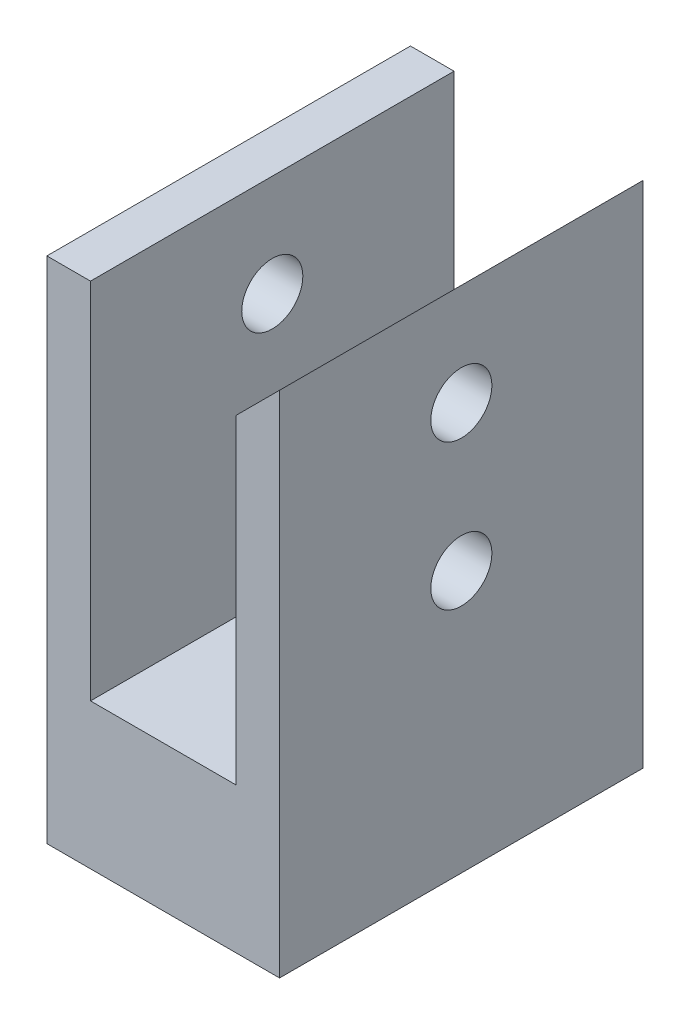
SolidWorks part; units mm, degrees
ref_plane "前视基准面" through (0, 0, 0) normal (0, 0, 1) x (1, 0, 0)
ref_plane "上视基准面" through (0, 0, 0) normal (0, 1, 0) x (1, 0, 0)
ref_plane "右视基准面" through (0, 0, 0) normal (1, 0, 0) x (0, 0, -1)
sketch "草图1" plane through (0, 0, 0) normal (0, 0, 1) x (1, 0, 0)
  line L0 (0, -55) -> (0, 55) construction
  line L1 (-8, -10) -> (8, -10)
  line L2 (-8, -10) -> (-8, 0)
  line L3 (-8, 0) -> (8, 0)
  line L4 (8, -10) -> (8, 0)
  line L5 (-8, -10) -> (8, 0) construction
  line L6 (-8, 0) -> (8, -10) construction
  line L7 (8, 0) -> (5, 0)
  line L8 (8, 0) -> (8, 25)
  line L9 (8, 25) -> (5, 25)
  line L10 (5, 0) -> (5, 25)
  line L11 (-8, 25) -> (-5, 25)
  line L12 (-5, 0) -> (-5, 25)
  line L13 (-8, 0) -> (-5, 0)
  line L14 (-8, 0) -> (-8, 25)
  line L15 (8, 25) -> (5, 22)
  point P0 (0, -5)
  point P14 (5, 22)
  dimension "D1" = 5
  dimension "D2" = 16
  dimension "D3" = 10
  dimension "D4" = 25
  dimension "D5" = 3
  dimension "D6" = 3
extrude "凸台-拉伸1" add sketch "草图1" along normal blind 25 contours L14 L3 L12 L11 | L10 L3 L8 L9 | L1 L4 L3 L2 region at (0, -5, 0) region at (-6.5, 12.5, 0) region at (6.5319, 11.766, 0)
sketch "草图2" plane through (0, 0, 0) normal (1, 0, 0) x (0, 0, -1)
  line L0 (0, -10) -> (0, 25) construction
  circle A0 centre (-12.5, 8) radius 2.1
  circle A1 centre (-12.5, 18) radius 2.1
  dimension "D1" = 4.2
  dimension "D2" = 8
  dimension "D3" = 12.5
  dimension "D4" = 2
extrude "切除-拉伸1" cut sketch "草图2" against normal through all
extrude "切除-拉伸2" cut sketch "草图2<2>" against normal through all both and the other way through all
sketch "草图2<2>" plane through (0, 0, 0) normal (1, 0, 0) x (0, 0, -1) same geometry as "草图2"
